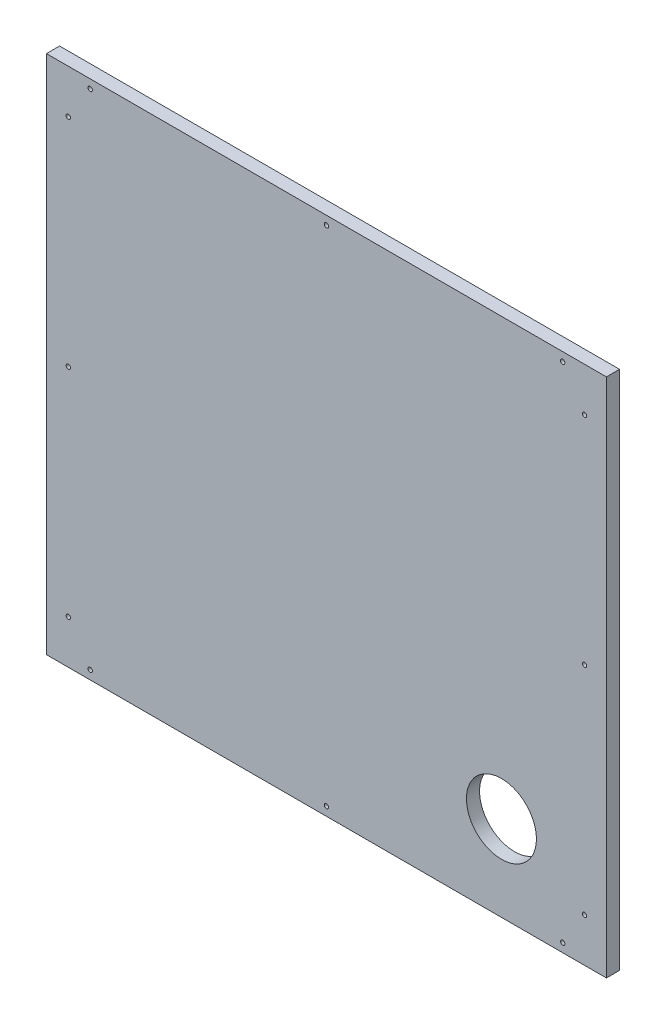
SolidWorks part; units mm, degrees
material "西洋杉"
ref_plane "正面" through (0, 0, 0) normal (0, 0, 1) x (1, 0, 0)
ref_plane "平面" through (0, 0, 0) normal (0, 1, 0) x (1, 0, 0)
ref_plane "右側面" through (0, 0, 0) normal (1, 0, 0) x (0, 0, -1)
sketch "ｽｹｯﾁ1" plane through (0, 0, 0) normal (0, 0, 1) x (1, 0, 0)
  line L1 (-320, 297.5) -> (320, 297.5)
  line L2 (-320, 297.5) -> (-320, -297.5)
  line L3 (-320, -297.5) -> (320, -297.5)
  line L4 (320, 297.5) -> (320, -297.5)
  line L5 (-320, 297.5) -> (320, -297.5) construction
  line L6 (-320, -297.5) -> (320, 297.5) construction
  point P0 (0, 0)
  dimension "D1" = 595
  dimension "D2" = 640
extrude "ﾎﾞｽ - 押し出し1" add sketch "ｽｹｯﾁ1" along normal blind 15
sketch "ｽｹｯﾁ2" plane through (0, 0, 15) normal (0, 0, 1) x (1, 0, 0)
  line L0 (-295, 297.5) -> (-295, -297.5) construction
  line L1 (320, 297.5) -> (-320, 297.5) construction
  line L2 (-320, -297.5) -> (320, -297.5) construction
  line L3 (-320, 297.5) -> (-320, -297.5) construction
  line L4 (-320, 287.5) -> (320, 287.5) construction
  line L5 (320, -297.5) -> (320, 297.5) construction
  circle A0 centre (-295, 247.5) radius 2.5
  circle A1 centre (-295, 0) radius 2.5
  circle A2 centre (-295, -247.5) radius 2.5
  circle A3 centre (-270, 287.5) radius 2.5
  circle A4 centre (0, 287.5) radius 2.5
  circle A5 centre (270, 287.5) radius 2.5
  point P20 (0, 0)
  dimension "D2" = 5
  dimension "D7" = 5
  dimension "D1" = 25
  dimension "D3" = 50
  dimension "D5" = 10
  dimension "D6" = 640
  dimension "D8" = 50
  dimension "D10" = 595
  dimension "D11" = 247.5
  dimension "D12" = 270
  dimension "D4" = 3
  dimension "D9" = 3
extrude "ｶｯﾄ - 押し出し1" cut sketch "ｽｹｯﾁ2" against normal through all contours A3 | A4 | A5
extrude "ｶｯﾄ - 押し出し2" cut sketch "ｽｹｯﾁ2<3>" against normal through all contours A0 | A1 | A2
sketch "ｽｹｯﾁ2<3>" plane through (0, 0, 15) normal (0, 0, 1) x (1, 0, 0) same geometry as "ｽｹｯﾁ2"
mirror "ﾐﾗｰ1" about plane through (0, 0, 0) normal (0, 1, 0) of "ｶｯﾄ - 押し出し1"
mirror "ﾐﾗｰ2" about plane through (0, 0, 0) normal (1, 0, 0) of "ｶｯﾄ - 押し出し2"
sketch "ｽｹｯﾁ3" plane through (0, 0, 15) normal (0, 0, 1) x (1, 0, 0)
  line L0 (200, 297.5) -> (200, -297.5) construction
  line L1 (320, 297.5) -> (-320, 297.5) construction
  line L2 (-320, -297.5) -> (320, -297.5) construction
  line L3 (-320, -200) -> (320, -200) construction
  line L4 (-320, 297.5) -> (-320, -297.5) construction
  line L5 (320, -297.5) -> (320, 297.5) construction
  circle A0 centre (200, -200) radius 40
  dimension "D3" = 80
  dimension "D1" = 200
  dimension "D2" = 200
extrude "ｶｯﾄ - 押し出し3" cut sketch "ｽｹｯﾁ3" against normal through all
equation "\"D11@ｽｹｯﾁ2\"=(\"D10@ｽｹｯﾁ2\"-100)/2"
equation "\"D12@ｽｹｯﾁ2\"=(\"D6@ｽｹｯﾁ2\"-100)/2"
